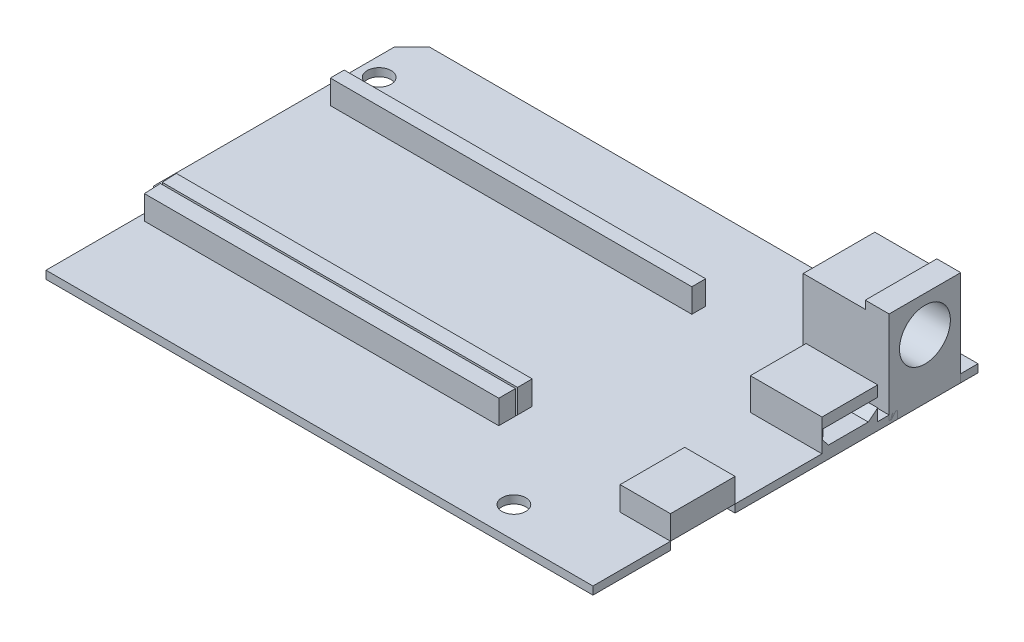
SolidWorks part; units mm, degrees
ref_plane "Front" through (0, 0, 0) normal (0, 0, 1) x (1, 0, 0)
ref_plane "Top" through (0, 0, 0) normal (0, 1, 0) x (1, 0, 0)
ref_plane "Right" through (0, 0, 0) normal (1, 0, 0) x (0, 0, -1)
sketch "Croquis2" plane through (0, 0, 0) normal (0, 1, 0) x (1, 0, 0)
  line L0 (-19.9498, 97.1711) -> (208.1221, 97.1711) construction
  line L1 (-183.1773, 45.3508) -> (-185.3464, 43.1818)
  line L2 (-114.206, 45.3508) -> (-114.206, -3.0359)
  line L3 (-114.206, -3.0359) -> (-182.9443, -3.0359)
  line L4 (-182.9443, -3.0359) -> (-182.9443, 10.4962)
  line L5 (-182.9443, 10.4962) -> (-185.3464, 12.8983)
  line L6 (-185.3464, 12.8983) -> (-185.3464, 43.1818)
  line L7 (-183.1773, 45.3508) -> (-114.206, 45.3508)
  line L8 (-182.2891, 12.6894) -> (-182.0968, 8.4834)
  line L9 (-182.9941, 34.4836) -> (-137.5639, 34.4836)
  line L10 (-182.9941, 34.4836) -> (-182.9941, 32.743)
  line L11 (-182.9941, 32.743) -> (-137.5639, 32.743)
  line L12 (-137.5639, 34.4836) -> (-137.5639, 32.743)
  line L13 (-182.2891, 12.6894) -> (-137.5639, 12.6894)
  line L14 (-182.9443, 10.4962) -> (-182.9443, 8.4834)
  line L15 (-182.0968, 8.4834) -> (-137.5639, 8.4834)
  line L16 (-137.5639, 12.6894) -> (-137.5639, 8.4834)
  line L17 (-120.5359, 14.8221) -> (-114.206, 14.8221)
  line L18 (-120.5359, 14.8221) -> (-120.5359, 6.7039)
  line L19 (-120.5359, 6.7039) -> (-114.206, 6.7039)
  line L20 (-114.206, 14.8221) -> (-114.206, 6.7039)
  line L21 (-118.6351, 32.743) -> (-114.206, 32.743)
  line L22 (-118.6351, 32.743) -> (-118.6351, 25.8224)
  line L23 (-118.6351, 25.8224) -> (-114.206, 25.8224)
  line L24 (-114.206, 32.743) -> (-114.206, 25.8224)
  line L25 (-125.1002, 43.1818) -> (-114.206, 43.1818)
  line L26 (-125.1002, 43.1818) -> (-125.1002, 35.2257)
  line L27 (-125.1002, 35.2257) -> (-114.206, 35.2257)
  line L28 (-114.206, 43.1818) -> (-114.206, 35.2257)
  line L29 (-182.193, 10.5864) -> (-137.5639, 10.5864)
  circle A0 centre (-127.0707, 43.6839) radius 1.5
  circle A1 centre (-128.0373, 0.8558) radius 1.5
  circle A2 centre (-182.9941, 38.8858) radius 1.5
  circle A3 centre (-183.1867, 14.1697) radius 1.5
  dimension "D1" = 3
extrude "Saliente-Extruir2" add sketch "Croquis2" along normal blind 1 contours L27 L26 L25 L2 L7 L1 L6 L5 L4 L3 L19 L18 L17 L23 L22 L21 A3 A2 A1 A0 L9 L12 L11 L10 L13 L16 L15 L8 region at (-150.1555, 0, -21.2146)
sketch "Croquis3" plane through (0, 1, 0) normal (0, 1, 0) x (1, 0, 0)
  line L1 (-114.206, 43.1818) -> (-125.006, 43.1818)
  line L2 (-114.206, 43.1818) -> (-114.206, 34.1818)
  line L3 (-114.206, 34.1818) -> (-125.006, 34.1818)
  line L4 (-125.006, 43.1818) -> (-125.006, 34.1818)
  point P4 (-125.006, 38.6818)
  dimension "D1" = 9
  dimension "D2" = 10.8
extrude "Saliente-Extruir5" add sketch "Croquis3" along normal blind 11 and the other way blind 1 separate body
sketch "Croquis4" plane through (-114.206, 0, 0) normal (1, 0, 0) x (0, 0, -1)
  line L0 (45.3508, 1) -> (43.1818, 1) construction
  line L1 (34.1818, 0) -> (34.1818, 12) construction
  circle A0 centre (38.6818, 7.5) radius 3.2
  dimension "D1" = 6.5
  dimension "D3" = 6.4
  dimension "D2" = 4.5
extrude "Cortar-Extruir1" cut sketch "Croquis4" against normal blind 5
sketch "Croquis5" plane through (0, 12, 0) normal (0, 1, 0) x (1, 0, 0)
  line L0 (-117.206, 43.1818) -> (-117.206, 34.1818)
  line L4 (-114.206, 34.1818) -> (-114.206, 43.1818)
  line L5 (-114.206, 43.1818) -> (-125.006, 43.1818)
  line L6 (-125.006, 43.1818) -> (-125.006, 34.1818)
  line L7 (-125.006, 34.1818) -> (-114.206, 34.1818)
  line L8 (-114.206, 34.1818) -> (-114.206, 43.1818)
  line L9 (-114.206, 43.1818) -> (-125.006, 43.1818)
  line L10 (-125.006, 43.1818) -> (-125.006, 34.1818)
  line L11 (-125.006, 34.1818) -> (-114.206, 34.1818)
  point P6 (-117.206, 38.6818)
  line M6 (-114.206, 43.1818) -> (-125.006, 43.1818)
  line M7 (-125.006, 43.1818) -> (-125.006, 34.1818)
  line M8 (-125.006, 34.1818) -> (-114.206, 34.1818)
  dimension "D2" = 3
  dimension "D1" = 0
extrude "Cortar-Extruir2" cut sketch "Croquis5" against normal blind 1 contours L0 M6 M7 M8 region at (-121.106, 12, -38.6818)
sketch "Croquis6" plane through (0, 1, 0) normal (0, 1, 0) x (1, 0, 0)
  line L1 (-114.206, 32.743) -> (-123.206, 32.743)
  line L2 (-114.206, 32.743) -> (-114.206, 25.743)
  line L3 (-114.206, 25.743) -> (-123.206, 25.743)
  line L4 (-123.206, 32.743) -> (-123.206, 25.743)
  dimension "D1" = 9
  dimension "D2" = 7
extrude "Saliente-Extruir6" add sketch "Croquis6" along normal blind 4 and the other way blind 1
sketch "Croquis7" plane through (-114.206, 0, 0) normal (1, 0, 0) x (0, 0, -1)
  line L0 (25.8665, 3.6435) -> (32.7525, 3.6435)
  line L1 (32.7525, 3.6435) -> (32.7525, 2.5055)
  line L2 (32.7525, 2.5055) -> (31.5618, 1.5435)
  line L3 (31.5618, 1.5435) -> (26.5618, 1.5435)
  line L4 (26.5618, 1.5435) -> (25.8307, 2.4484)
  line L5 (25.8307, 2.4484) -> (25.8665, 3.6435)
  point P7 (32.7525, 3.0745)
  dimension "D1" = 5
  dimension "D2" = 2.1
  dimension "D3" = 6.9
extrude "Cortar-Extruir3" cut sketch "Croquis7" against normal blind 4
sketch "Croquis8" plane through (0, 1, 0) normal (0, 1, 0) x (1, 0, 0)
  line L0 (-114.206, 6.7039) -> (-114.206, -3.0359) construction
  line L1 (-120.5359, 14.8221) -> (-114.206, 14.8221)
  line L2 (-120.5359, 14.8221) -> (-120.5359, 6.7039)
  line L3 (-120.5359, 6.7039) -> (-114.206, 6.7039)
  line L4 (-114.206, 14.8221) -> (-114.206, 6.7039)
extrude "Saliente-Extruir7" add sketch "Croquis8" along normal blind 3 separate body
sketch "Croquis9" plane through (0, 1, 0) normal (0, 1, 0) x (1, 0, 0)
  line L0 (-182.9941, 34.4836) -> (-182.9941, 32.743) construction
  line L1 (-182.9941, 32.743) -> (-137.5639, 32.743) construction
  line L2 (-182.9941, 34.4836) -> (-137.5639, 34.4836) construction
  line L3 (-137.5639, 34.4836) -> (-137.5639, 32.743) construction
  line L4 (-182.9941, 34.4836) -> (-182.9941, 32.743)
  line L5 (-137.5639, 34.4836) -> (-137.5639, 32.743)
  line L6 (-182.9941, 34.4836) -> (-137.5639, 34.4836)
  line L7 (-182.9941, 32.743) -> (-137.5639, 32.743)
  line L8 (-137.5639, 12.6894) -> (-137.5639, 8.4834) construction
  line L9 (-182.2891, 12.6894) -> (-182.0968, 8.4834) construction
  line L10 (-182.0968, 8.4834) -> (-137.5639, 8.4834) construction
  line L11 (-182.2891, 12.6894) -> (-137.5639, 12.6894) construction
  line L12 (-137.5639, 12.6894) -> (-137.5639, 8.4834)
  line L13 (-182.2891, 12.6894) -> (-182.0968, 8.4834)
  line L14 (-182.0968, 8.4834) -> (-137.5639, 8.4834)
  line L15 (-182.2891, 12.6894) -> (-137.5639, 12.6894)
  line L16 (-182.2043, 10.8336) -> (-137.5639, 10.8336)
  line L17 (-182.193, 10.5864) -> (-137.5639, 10.5864)
  line M24 (-182.9941, 34.4836) -> (-137.5639, 34.4836)
  line M25 (-137.5639, 34.4836) -> (-137.5639, 32.743)
  line M26 (-137.5639, 32.743) -> (-182.9941, 32.743)
  line M27 (-182.9941, 32.743) -> (-182.9941, 34.4836)
  line M28 (-182.2891, 12.6894) -> (-137.5639, 12.6894)
  line M29 (-137.5639, 12.6894) -> (-137.5639, 8.4834)
  line M30 (-137.5639, 8.4834) -> (-182.0968, 8.4834)
  line M31 (-182.0968, 8.4834) -> (-182.2891, 12.6894)
extrude "Saliente-Extruir8" add sketch "Croquis9" along normal blind 3 and the other way blind 1 contours L13 L16 M29 M28 | L17 M31 M30 M29 | M24 M27 M26 M25 region at (-160.279, 1, -33.6133) region at (-159.9053, 1, -11.7618) region at (-159.8544, 1, -9.5352)
